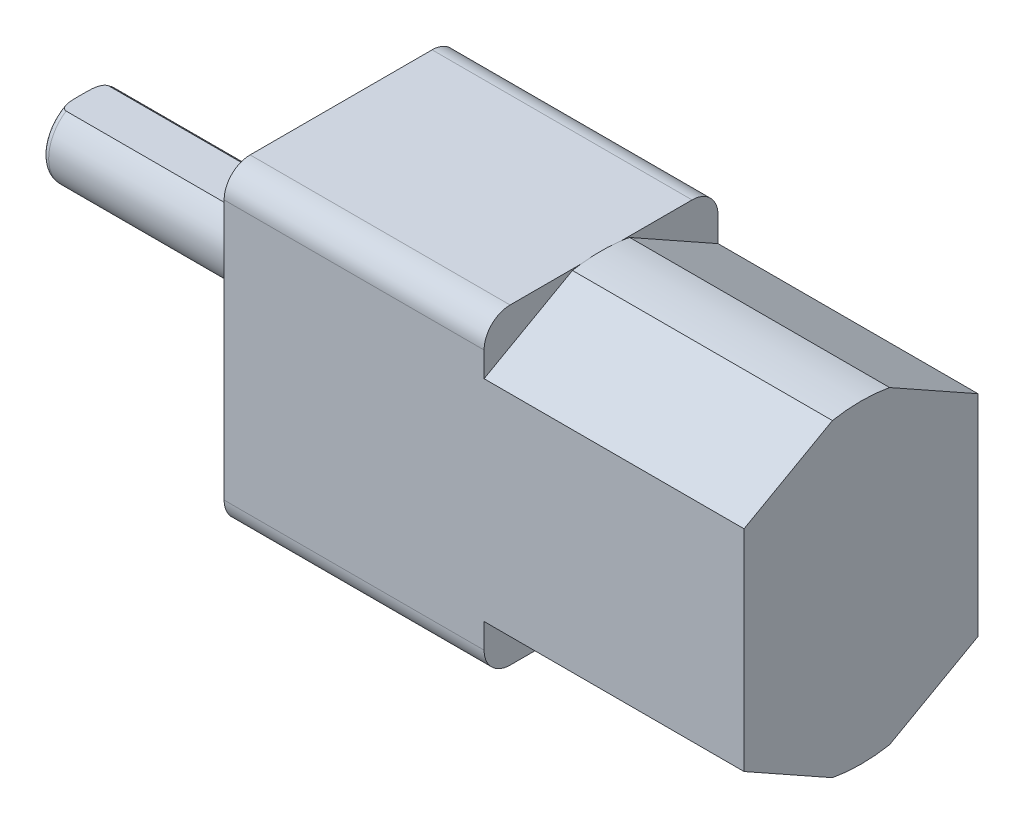
SolidWorks part; units mm, degrees
ref_plane "Front Plane" through (0, 0, 0) normal (0, 0, 1) x (1, 0, 0)
ref_plane "Top Plane" through (0, 0, 0) normal (0, 1, 0) x (1, 0, 0)
ref_plane "Right Plane" through (0, 0, 0) normal (1, 0, 0) x (0, 0, -1)
sketch "Sketch1" plane through (0, 0, 0) normal (0, 0, 1) x (1, 0, 0)
  line L0 (0, 6) -> (0, -6) construction
  line L1 (-5, -6) -> (5, -6)
  line L2 (-5, -6) -> (-5, 6)
  line L3 (-5, 6) -> (5, 6)
  line L4 (5, -6) -> (5, 6)
  line L5 (-5, -6) -> (5, 6) construction
  line L6 (-5, 6) -> (5, -6) construction
  line L7 (0, 0) -> (-5, 0) construction
  circle A0 centre (0, 4.5) radius 0.7
  circle A1 centre (0, -4.5) radius 0.7
  point P0 (0, 0)
  dimension "D4" = 1.4
  dimension "D1" = 12
  dimension "D2" = 10
  dimension "D3" = 9
extrude "Boss-Extrude1" add sketch "Sketch1" against normal blind 9 contours A0 | A1 | L1 L4 L3 L2 A0 A1 | A0 | A1 | L2 L1 L4 L3 region at (0, 0, 0) region at (0, 4.5, 0) region at (0, -4.5, 0)
sketch "Sketch2" plane through (5, 0, 0) normal (1, 0, 0) x (0, 0, -1)
  line L0 (0, 0) -> (9, 0) construction
  line L1 (9, -6) -> (9, 6) construction
  line L2 (0, 4.0438) -> (3.4, 5.9492)
  line L3 (0, -6) -> (0, 6) construction
  line L4 (0, 4.0438) -> (0, -4.0438)
  line L5 (0, -4.0438) -> (3.4, -5.9492)
  line L6 (4.5, 6) -> (4.5, -6) construction
  line L7 (9, 6) -> (0, 6) construction
  line L8 (9, -6) -> (0, -6) construction
  line L9 (9, -4.0438) -> (5.6, -5.9492)
  line L10 (9, 4.0438) -> (9, -4.0438)
  line L11 (9, 4.0438) -> (5.6, 5.9492)
  arc A0 (0, -4.0438) -> (9, -4.0438) centre (4.5, 0) ccw
  arc A1 (9, 4.0438) -> (0, 4.0438) centre (4.5, 0) ccw
  line M7 (0, 6) -> (0, -6)
  line M8 (0, -6) -> (9, -6)
  line M9 (9, -6) -> (9, 6)
  line M10 (9, 6) -> (0, 6)
  dimension "D1" = 12.1
  dimension "D2" = 3.4
extrude "Boss-Extrude2" add sketch "Sketch2" along normal blind 10 contours L11 A1 L2 L5 A0 L9 M10 M7 M8 M9 | A1 M10 | A0 M8 region at (5, 0, -4.5) region at (5, 6.02, -4.5) region at (5, -6.02, -4.5)
sketch "Sketch3" plane through (15, 0, 0) normal (1, 0, 0) x (0, 0, -1)
  line L0 (9, 4.0438) -> (5.6, 5.9492) construction
  line L1 (0, -6) -> (14.5, -6)
  line L2 (0, -6) -> (0, 6)
  line L3 (0, 6) -> (14.5, 6)
  line L4 (14.5, -6) -> (14.5, 6)
  line L5 (9, 4.0438) -> (5.6, 5.9492)
  line L6 (0, 4.0438) -> (3.4, 5.9492) construction
  line L7 (9, -4.0438) -> (9, 4.0438) construction
  line L8 (9, -4.0438) -> (5.6, -5.9492) construction
  line L9 (0, -4.0438) -> (3.4, -5.9492) construction
  line L10 (0, -4.0438) -> (3.4, -5.9492)
  line L11 (9, -4.0438) -> (5.6, -5.9492)
  line L12 (9, -4.0438) -> (9, 4.0438)
  line L13 (0, 4.0438) -> (3.4, 5.9492)
  line M5 (9, 4.0438) -> (5.6, 5.9492)
  arc M6 (5.6, 5.9492) -> (3.4, 5.9492) centre (4.5, 0) ccw
  arc M10 (3.4, -5.9492) -> (5.6, -5.9492) centre (4.5, 0) ccw
  line M11 (5.6, -5.9492) -> (9, -4.0438)
  line M12 (9, -4.0438) -> (9, 4.0438)
  dimension "D1" = 12
  dimension "D2" = 14.5
extrude "Boss-Extrude3" [suppressed] add sketch "Sketch3" against normal blind 5 contours L1 L4 L3 M6 M5 M12 M11 M10
sketch "Sketch4" plane through (-5, 0, 0) normal (-1, 0, 0) x (0, 0, 1)
  line L0 (0, 0) -> (-9, 0) construction
  line L1 (-5.3292, 1.25) -> (-3.6708, 1.25)
  line L4 (0, -6) -> (0, 6)
  line L5 (0, 6) -> (-9, 6)
  line L6 (-9, 6) -> (-9, -6)
  line L7 (-9, -6) -> (0, -6)
  line L8 (0, -6) -> (0, 6)
  line L9 (0, 6) -> (-9, 6)
  line L10 (-9, 6) -> (-9, -6)
  line L11 (-9, -6) -> (0, -6)
  circle A0 centre (-4.5, 0) radius 2
  circle A1 centre (-4.5, 0) radius 1.5
  dimension "D2" = 4
  dimension "D3" = 3
  dimension "D4" = 2.5
  dimension "D1" = 0
extrude "Boss-Extrude4" add sketch "Sketch4" along normal blind 0.7 contours L0 A0 A1 | A0 L0 A1 | L0 A1 L1 | L1 A1 | A1 L0 region at (-5, -1.9553, -4.5) region at (-5, 0.0447, -2.75) region at (-5, -0.6366, -4.5) region at (-5, 0.5749, -4.5) region at (-5, 1.3508, -4.5)
extrude "Boss-Extrude5" add sketch "Sketch4<3>" along normal blind 10 contours L0 A1 L1 | A1 L0 region at (-5, -0.6366, -4.5) region at (-5, 0.5749, -4.5)
sketch "Sketch4<3>" plane through (-5, 0, 0) normal (-1, 0, 0) x (0, 0, 1) same geometry as "Sketch4"
fillet "Fillet1" radius 1 4 edges at (0, -6, 0) (0, -6, -9) (0, 6, 0) (0, 6, -9)
fillet "Fillet2" radius 0.25 1 edges at (-15, -1.5, -4.5)
